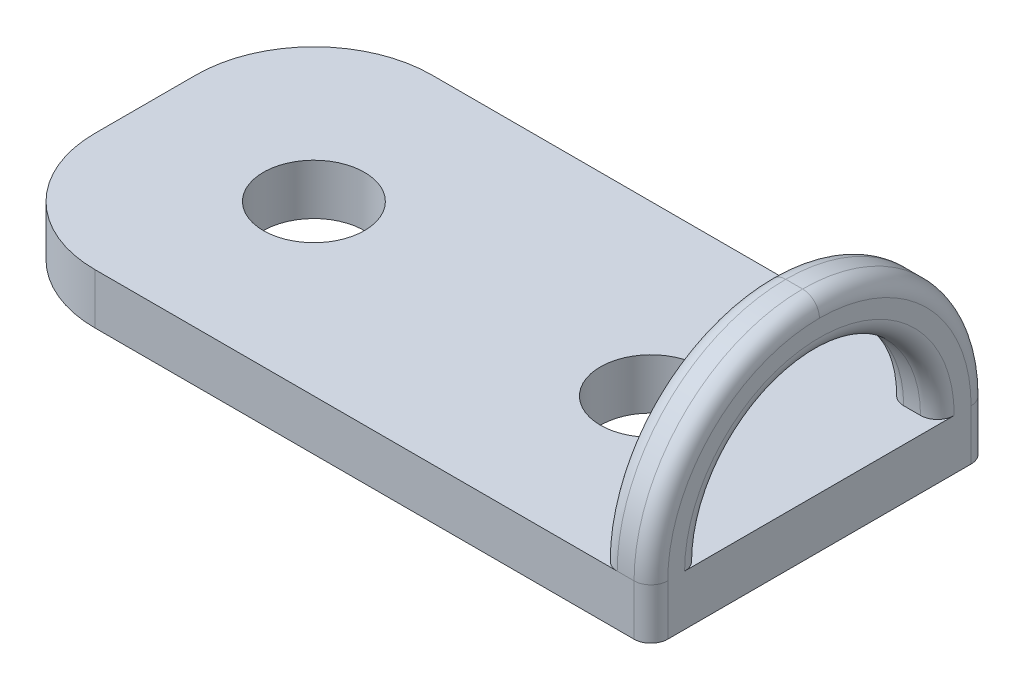
SolidWorks part; units mm, degrees
ref_plane "Front Plane" through (0, 0, 0) normal (0, 0, 1) x (1, 0, 0)
ref_plane "Top Plane" through (0, 0, 0) normal (0, 1, 0) x (1, 0, 0)
ref_plane "Right Plane" through (0, 0, 0) normal (1, 0, 0) x (0, 0, -1)
sketch "Sketch1" plane through (0, 0, 0) normal (0, 1, 0) x (1, 0, 0)
  line L0 (-40, -10) -> (0, -10) construction
  line L1 (0, 0) -> (-33, 0)
  line L2 (0, 0) -> (0, -20)
  line L3 (0, -20) -> (-33, -20)
  line L4 (-40, -7) -> (-40, -13)
  circle A0 centre (-30, -10) radius 3
  circle A1 centre (-10, -10) radius 3
  arc A2 (-33, -20) -> (-40, -13) centre (-33, -13) cw
  arc A3 (-33, 0) -> (-40, -7) centre (-33, -7) ccw
  point P13 (-40, -20)
  point P16 (-40, 0)
  dimension "D3" = 6
  dimension "D6" = 7
  dimension "D1" = 40
  dimension "D2" = 20
  dimension "D4" = 10
  dimension "D5" = 20
extrude "Boss-Extrude1" add sketch "Sketch1" along normal blind 3
sketch "Sketch2" plane through (0, 3, 0) normal (0, 1, 0) x (1, 0, 0)
  line L0 (-33, -20) -> (0, -20) construction
  line L1 (0, 0) -> (-3, 0)
  line L2 (0, 0) -> (0, -20)
  line L3 (0, -20) -> (-3, -20)
  line L4 (-3, 0) -> (-3, -20)
  line M5 (0, -20) -> (0, 0)
  line M6 (0, 0) -> (-33, 0)
  line M10 (-33, -20) -> (0, -20)
  dimension "D1" = 3
extrude "Boss-Extrude2" add sketch "Sketch2" along normal blind 10 contours L4 M6 M10 M5 | L2 L1 L4 L3 region at (-1.5, 3, 10)
fillet "Fillet1" radius 10 2 edges at (-1.5, 13, 0) (-1.5, 13, 20)
sketch "Sketch3" plane through (-3, 0, 0) normal (-1, 0, 0) x (0, 0, 1)
  line L0 (7, 3) -> (0, 3) construction
  line L1 (20, 3) -> (13, 3) construction
  line L2 (7, 3) -> (13, 3) construction
  line L3 (3, 3) -> (17, 3)
  arc A0 (3, 3) -> (17, 3) centre (10, 3) cw
  arc A2 (10, 13) -> (0, 3) centre (10, 3) ccw construction
  dimension "D1" = 3
extrude "Cut-Extrude1" cut sketch "Sketch3" against normal through all
fillet "Fillet2" radius 1 8 edges at (0, 1.5, 0) (0, 1.5, 20) (0, 10.0711, 17.0711) (-3, 10.0711, 17.0711) (0, 10, 10) (-3, 10, 10) (0, 10.0711, 2.9289) (-3, 10.0711, 2.9289)
